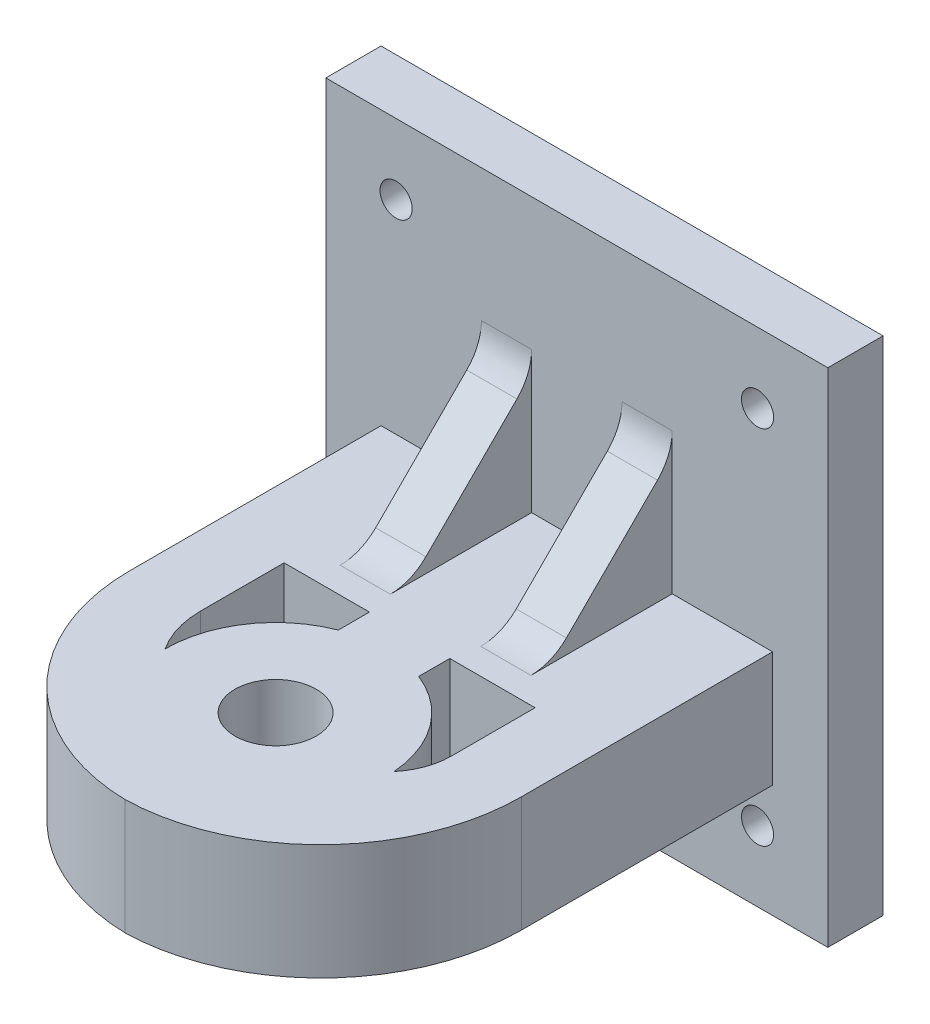
SolidWorks part; units mm, degrees
ref_plane "Front Plane" through (0, 0, 0) normal (0, 0, 1) x (1, 0, 0)
ref_plane "Top Plane" through (0, 0, 0) normal (0, 1, 0) x (1, 0, 0)
ref_plane "Right Plane" through (0, 0, 0) normal (1, 0, 0) x (0, 0, -1)
sketch "Sketch1" plane through (0, 0, 0) normal (0, 1, 0) x (1, 0, 0)
  line L1 (0, 0) -> (39, 0)
  line L2 (0, 0) -> (0, 45)
  line L3 (0, 45) -> (39, 45)
  line L4 (39, 0) -> (39, 45)
  dimension "D1" = 39
  dimension "D2" = 45
extrude "Boss-Extrude1" add sketch "Sketch1" along normal blind 12.5
sketch "Sketch2" plane through (0, 12.5, 0) normal (0, 1, 0) x (1, 0, 0)
  line L0 (19.5, 45) -> (19.5, 0) construction
  line L1 (39, 45) -> (0, 45) construction
  line L2 (0, 0) -> (39, 0) construction
  circle A0 centre (19.5, 15) radius 4.05
  dimension "D2" = 8.1
  dimension "D1" = 30
extrude "Cut-Extrude1" cut sketch "Sketch2" against normal through all
sketch "Sketch3" plane through (0, 0, -45) normal (0, 0, -1) x (-1, 0, 0)
  line L0 (-19.5, 12.5) -> (-19.5, 0) construction
  line L1 (-44.5, -10.25) -> (5.5, -10.25)
  line L2 (-44.5, -10.25) -> (-44.5, 39.75)
  line L3 (-44.5, 39.75) -> (5.5, 39.75)
  line L4 (5.5, -10.25) -> (5.5, 39.75)
  line L5 (-39, 12.5) -> (0, 12.5) construction
  line L6 (-39, 0) -> (0, 0) construction
  line L7 (-39, 6.25) -> (0, 6.25) construction
  line L8 (-39, 12.5) -> (-39, 0) construction
  line L9 (0, 12.5) -> (0, 0) construction
  dimension "D1" = 50
  dimension "D2" = 25
  dimension "D3" = 50
  dimension "D4" = 16.5
extrude "Boss-Extrude2" add sketch "Sketch3" along normal blind 5.5
sketch "Sketch4" plane through (39, 0, 0) normal (1, 0, 0) x (0, 0, -1)
  line L0 (33, 12.5) -> (45, 24.5)
  line L1 (0, 12.5) -> (45, 12.5) construction
  line L2 (45, 39.75) -> (45, -10.25) construction
  line L3 (45, 24.5) -> (45, 12.5)
  line L4 (45, 12.5) -> (45, 0) construction
  line L5 (45, 12.5) -> (33, 12.5)
  dimension "D1" = 12
  dimension "D2" = 12
extrude "Boss-Extrude3" add sketch "Sketch4" against normal blind 5 from offset 10 offset against normal yes
pattern_linear "LPattern1" count 2 spacing 14 along (-1, 0, 0) of "Boss-Extrude3"
fillet "Fillet1" radius 5 4 edges at (26.5, 24.5, -45) (12.5, 24.5, -45) (12.5, 12.5, -33) (26.5, 12.5, -33)
sketch "Sketch5" plane through (0, 0, -50.5) normal (0, 0, -1) x (-1, 0, 0)
  line L0 (-19.5, 39.75) -> (-19.5, -10.25) construction
  line L1 (5.5, 39.75) -> (-44.5, 39.75) construction
  line L2 (-44.5, -10.25) -> (5.5, -10.25) construction
  line L3 (-44.5, 14.75) -> (5.5, 14.75) construction
  line L4 (-44.5, 39.75) -> (-44.5, -10.25) construction
  line L5 (5.5, -10.25) -> (5.5, 39.75) construction
  circle A0 centre (-37.5, 32.75) radius 1.6
  circle A1 centre (-1.5, 32.75) radius 1.6
  circle A2 centre (-1.5, -3.25) radius 1.6
  circle A3 centre (-37.5, -3.25) radius 1.6
  dimension "D5" = 3.2
  dimension "D6" = 3.2
  dimension "D7" = 3.2
  dimension "D8" = 3.2
  dimension "D1" = 36
  dimension "D2" = 36
  dimension "D3" = 7
  dimension "D4" = 7
extrude "Cut-Extrude2" cut sketch "Sketch5" against normal through all
fillet "Fillet2" radius 20 2 edges at (0, 6.25, 0) (39, 6.25, 0)
sketch "Sketch6" plane through (0, 12.5, 0) normal (0, 1, 0) x (1, 0, 0)
  line L0 (0, 20) -> (39, 20) construction
  line L1 (0, 45) -> (0, 20) construction
  line L2 (39, 20) -> (39, 45) construction
  line L3 (7, 20) -> (7, 28.3476)
  line L4 (7, 28.3476) -> (15.5, 28.3476)
  line L5 (15.5, 28.3476) -> (15.5, 25.247)
  line L6 (23.5, 25.247) -> (23.5, 28.3476)
  line L7 (23.5, 28.3476) -> (32, 28.3476)
  line L8 (32, 28.3476) -> (32, 20)
  arc A0 (8.5, 15) -> (15.5, 25.247) centre (19.5, 15) cw
  arc A1 (30.4703, 15.8083) -> (23.5, 25.247) centre (19.5, 15) ccw
  arc A2 (19.5, 0.0063) -> (39, 20) centre (19, 20) ccw construction
  arc A3 (8.5, 15) -> (7, 20) centre (16.0833, 20) cw
  arc A4 (30.4703, 15.8083) -> (32, 20) centre (25.4923, 20) ccw
  dimension "D1" = 11
  dimension "D2" = 11
  dimension "D3" = 4
  dimension "D4" = 4
  dimension "D5" = 7
  dimension "D6" = 7
extrude "Cut-Extrude3" cut sketch "Sketch6" against normal through all
sketch "Sketch7" plane through (0, 0, 0) normal (0, -1, 0) x (1, 0, 0)
  line L0 (-0.1, -45) -> (39.1, -45)
  line L1 (39.1, -45) -> (39.1, 5.0637)
  line L2 (39.1, 5.0637) -> (-0.1, 5.0637)
  line L3 (-0.1, 5.0637) -> (-0.1, -45)
  line L4 (19.5, -10.95) -> (19.5, -19.05) construction
  line L5 (15.5, -28.3476) -> (15.5, -25.247) construction
  line L6 (4.5, -43.0018) -> (15.5, -43.0018)
  line L7 (4.5, -43.0018) -> (4.5, -32.0018)
  line L8 (4.5, -32.0018) -> (15.5, -32.0018)
  line L9 (15.5, -43.0018) -> (15.5, -32.0018)
  line L10 (23.5, -43.0018) -> (34.5, -43.0018)
  line L11 (23.5, -43.0018) -> (23.5, -32.0018)
  line L12 (23.5, -32.0018) -> (34.5, -32.0018)
  line L13 (34.5, -43.0018) -> (34.5, -32.0018)
  line L14 (23.5, -25.247) -> (23.5, -28.3476) construction
  circle A0 centre (19.5, -15) radius 4.05 construction
  circle A1 centre (19.5, -15) radius 11
  dimension "D1" = 22
  dimension "D2" = 11
  dimension "D3" = 11
  dimension "D4" = 11
  dimension "D5" = 11
extrude "Cut-Extrude4" cut sketch "Sketch7" against normal blind 1
sketch "Sketch8" plane through (0, 0, -50.5) normal (0, 0, -1) x (-1, 0, 0)
  line L0 (5.5, 39.75) -> (-44.5, 39.75) construction
  line L1 (-32, 35.25) -> (-7, 35.25)
  line L2 (-32, 35.25) -> (-32, 30.25)
  line L3 (-32, 30.25) -> (-7, 30.25)
  line L4 (-7, 35.25) -> (-7, 30.25)
  line L5 (-19.5, 39.75) -> (-19.5, -10.25) construction
  line L6 (-44.5, -10.25) -> (5.5, -10.25) construction
  line L7 (5.5, -10.25) -> (5.5, 39.75) construction
  line L8 (-4, 27.25) -> (1, 27.25)
  line L9 (-4, 27.25) -> (-4, 2.25)
  line L10 (-4, 2.25) -> (1, 2.25)
  line L11 (1, 27.25) -> (1, 2.25)
  line L12 (5.5, 14.75) -> (-44.5, 14.75) construction
  line L13 (-44.5, 39.75) -> (-44.5, -10.25) construction
  line L15 (-7, -0.75) -> (-32, -0.75)
  line L16 (-7, -0.75) -> (-7, -5.75)
  line L17 (-7, -5.75) -> (-32, -5.75)
  line L18 (-32, -0.75) -> (-32, -5.75)
  line L19 (-35, 27.25) -> (-40, 27.25)
  line L20 (-35, 27.25) -> (-35, 2.25)
  line L21 (-35, 2.25) -> (-40, 2.25)
  line L22 (-40, 27.25) -> (-40, 2.25)
  dimension "D1" = 5
  dimension "D2" = 4.5
  dimension "D3" = 25
  dimension "D4" = 12.5
  dimension "D5" = 4.5
  dimension "D6" = 5
  dimension "D7" = 25
  dimension "D8" = 12.5
  dimension "D9" = 4.5
  dimension "D10" = 5
  dimension "D11" = 25
  dimension "D12" = 12.5
  dimension "D13" = 4.5
  dimension "D14" = 5
  dimension "D15" = 25
  dimension "D16" = 12.5
extrude "Boss-Extrude4" add sketch "Sketch8" along normal blind 0.5
